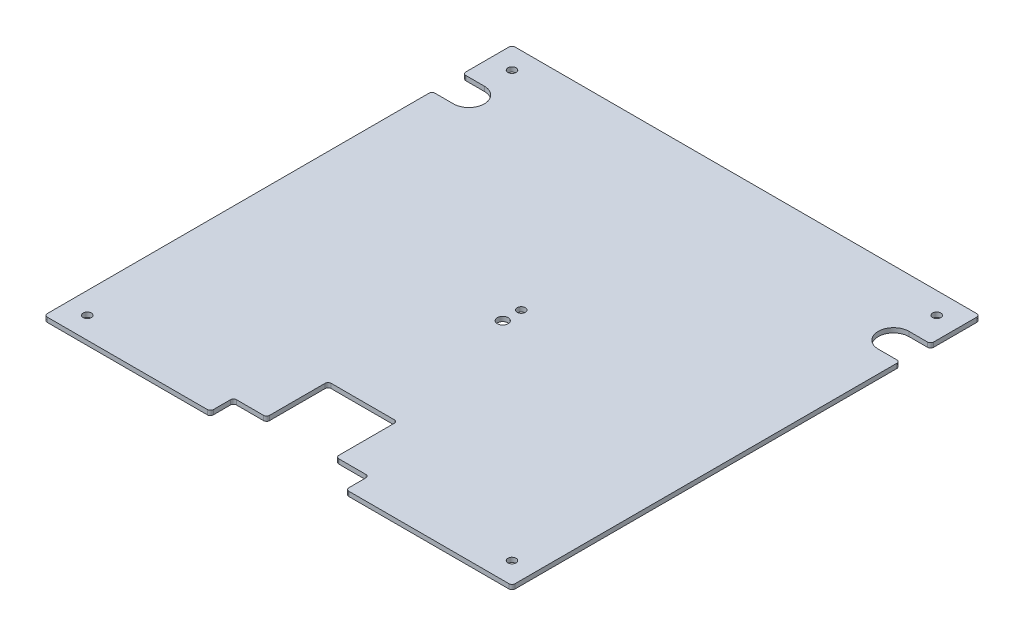
SolidWorks part; units mm, degrees
material "6061-T6 (SS)"
ref_plane "Front Plane" through (0, 0, 0) normal (0, 0, 1) x (1, 0, 0)
ref_plane "Top Plane" through (0, 0, 0) normal (0, 1, 0) x (1, 0, 0)
ref_plane "Right Plane" through (0, 0, 0) normal (1, 0, 0) x (0, 0, -1)
sketch "Sketch1" plane through (0, 0, 0) normal (0, 1, 0) x (1, 0, 0)
  line L1 (152, -152) -> (-152, -152)
  line L2 (152, -152) -> (152, 152)
  line L3 (152, 152) -> (-152, 152)
  line L4 (-152, -152) -> (-152, 152)
  line L5 (152, -152) -> (-152, 152) construction
  line L6 (152, 152) -> (-152, -152) construction
  point P0 (0, 0)
  dimension "D1" = 304
extrude "Boss-Extrude1" add sketch "Sketch1" along normal blind 3
sketch "Sketch2" plane through (0, 3, 0) normal (0, 1, 0) x (1, 0, 0)
  line L0 (-44, -152) -> (-44, -137)
  line L1 (-152, -152) -> (152, -152) construction
  line L2 (-44, -137) -> (44, -137)
  line L3 (44, -137) -> (44, -152)
  line L4 (44, -152) -> (-44, -152)
  line L5 (-152, 100) -> (-138, 100)
  line L6 (-152, 152) -> (-152, -152) construction
  line L8 (-138, 120) -> (-152, 120)
  line L9 (-152, 120) -> (-152, 100)
  line L10 (-152, 110) -> (-138, 110) construction
  line L11 (0, -152) -> (0, 152) construction
  line L12 (152, 152) -> (-152, 152) construction
  line L13 (152, 100) -> (138, 100)
  line L14 (152, 120) -> (152, 100)
  line L15 (138, 120) -> (152, 120)
  arc A0 (-138, 100) -> (-138, 120) centre (-138, 110) ccw
  arc A1 (138, 100) -> (138, 120) centre (138, 110) cw
  point P20 (0, 0)
  dimension "D1" = 108
  dimension "D2" = 196
  dimension "D3" = 15
  dimension "D4" = 20
  dimension "D5" = 262
  dimension "D6" = 14
extrude "Cut-Extrude1" cut sketch "Sketch2" against normal through all
sketch "Sketch7" plane through (0, 0, 0) normal (0, -1, 0) x (1, 0, 0)
  line L0 (44, 137) -> (-44, 137) construction
  line L1 (22.5, 97) -> (-22.5, 97)
  line L2 (22.5, 97) -> (22.5, 137)
  line L3 (22.5, 137) -> (-22.5, 137)
  line L4 (-22.5, 97) -> (-22.5, 137)
  line L5 (22.5, 97) -> (-22.5, 137) construction
  line L6 (22.5, 137) -> (-22.5, 97) construction
  point P0 (0, 117)
  dimension "D1" = 45
  dimension "D2" = 40
extrude "Cut-Extrude2" cut sketch "Sketch7" against normal up to surface (3 mm away) up to face at (0, 3, -18.875)
hole_wizard "Ø7.0 (7) Diameter Hole1" positions "Sketch3" profile "Sketch4" hole size "Ø7.0" standard "ANSI Metric" end condition up to next
sketch "Sketch3" plane through (0, 3, 0) normal (0, 1, 0) x (1, 0, 0)
  line L1 (-138, -138) -> (138, -138)
  line L2 (-138, -138) -> (-138, 138)
  line L3 (-138, 138) -> (138, 138)
  line L4 (138, -138) -> (138, 138)
  line L7 (0, 6) -> (0, -6) construction
  line L8 (-152, 100) -> (-152, -152) construction
  line L9 (-152, -152) -> (-44, -152) construction
  point P138 (0, -6)
  dimension "D1" = 14
  dimension "D2" = 152
  dimension "D3" = 290
  dimension "D4" = 14
  dimension "D5" = 146
  dimension "D6" = 158
  dimension "D7" = 290
sketch "Sketch4" plane through (0, 3, 6) normal (1, 0, 0) x (0, 0, 1)
  line L0 (0, 0) -> (0, 3)
  line L1 (0, 3) -> (3.5, 3)
  line L2 (3.5, 3) -> (3.5, 0)
  line L5 (3.5, 0) -> (0, 0)
  line L11 (0, -6.35) -> (0, 107.95) construction
  dimension "Thru Hole Dia." = 7
  dimension "Thru Hole Depth" = 3
hole_wizard "M5 Clearance Hole1" positions "Sketch5" profile "Sketch6" hole size "M5" standard "ANSI Metric" end condition up to next
sketch "Sketch5" plane through (0, 3, 0) normal (0, 1, 0) x (1, 0, 0)
  point P0 (-138, 138)
  point P3 (138, 138)
  point P6 (138, -138)
  point P9 (-138, -138)
  point P13 (0, 6)
sketch "Sketch6" plane through (-138, 3, -138) normal (1, 0, 0) x (0, 0, 1)
  line L0 (0, 0) -> (0, 3)
  line L1 (0, 3) -> (2.65, 3)
  line L2 (2.65, 3) -> (2.65, 0)
  line L5 (2.65, 0) -> (0, 0)
  line L11 (0, -6.35) -> (0, 107.95) construction
  dimension "Thru Hole Dia." = 5.3
  dimension "Thru Hole Depth" = 3
sketch "Sketch8" plane through (0, 3, 0) normal (0, 1, 0) x (1, 0, 0)
  line L1 (147.5, -147.5) -> (-147.5, -147.5)
  line L2 (147.5, -147.5) -> (147.5, 147.5)
  line L3 (147.5, 147.5) -> (-147.5, 147.5)
  line L4 (-147.5, -147.5) -> (-147.5, 147.5)
  line L5 (147.5, -147.5) -> (-147.5, 147.5) construction
  line L6 (147.5, 147.5) -> (-147.5, -147.5) construction
  point P0 (0, 0)
  dimension "D1" = 295
fillet "Fillet1" radius 2 16 edges at (22.5, 1.5, 97) (-22.5, 1.5, 97) (-22.5, 1.5, 137) (-44, 1.5, 137) (-44, 1.5, 152) (-152, 1.5, -100) (-152, 1.5, -120) (-152, 1.5, -152) (152, 1.5, -152) (152, 1.5, -120) (152, 1.5, -100) (152, 1.5, 152) (44, 1.5, 152) (44, 1.5, 137) (22.5, 1.5, 137) (-152, 1.5, 152)
